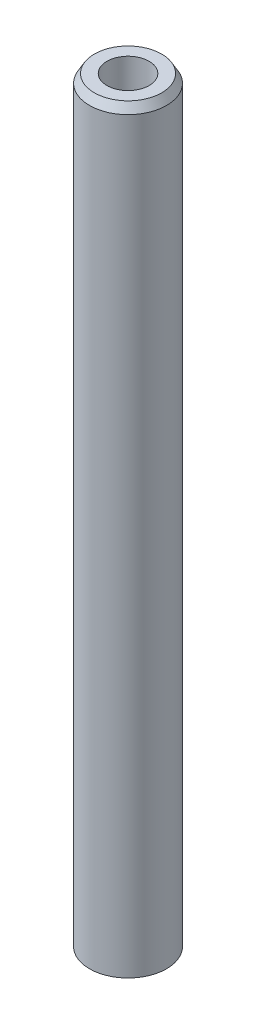
SolidWorks part; units mm, degrees
ref_plane "Front Plane" through (0, 0, 0) normal (0, 0, 1) x (1, 0, 0)
ref_plane "Top Plane" through (0, 0, 0) normal (0, 1, 0) x (1, 0, 0)
ref_plane "Right Plane" through (0, 0, 0) normal (1, 0, 0) x (0, 0, -1)
sketch "Sketch1" plane through (0, 0, 0) normal (0, 1, 0) x (1, 0, 0)
  circle A0 centre (0, 0) radius 25
  dimension "SHAFT_OD" = 50
extrude "Boss-Extrude1" add sketch "Sketch1" along normal blind 493.7579
sketch "Sketch2" plane through (0, 0, 0) normal (0, 1, 0) x (1, 0, 0)
  circle A0 centre (0, 0) radius 13.6731
  dimension "BORE_D" = 27.3462
extrude "Cut-Extrude1" cut sketch "Sketch2" along normal through all
chamfer "Chamfer1" distance 5.5128 angle 30 2 edges at (0, 493.7579, 25) (0, 0, 25) first distance on face at (0, 493.7579, 25) first distance on face at (0, 0, 13.6731)
